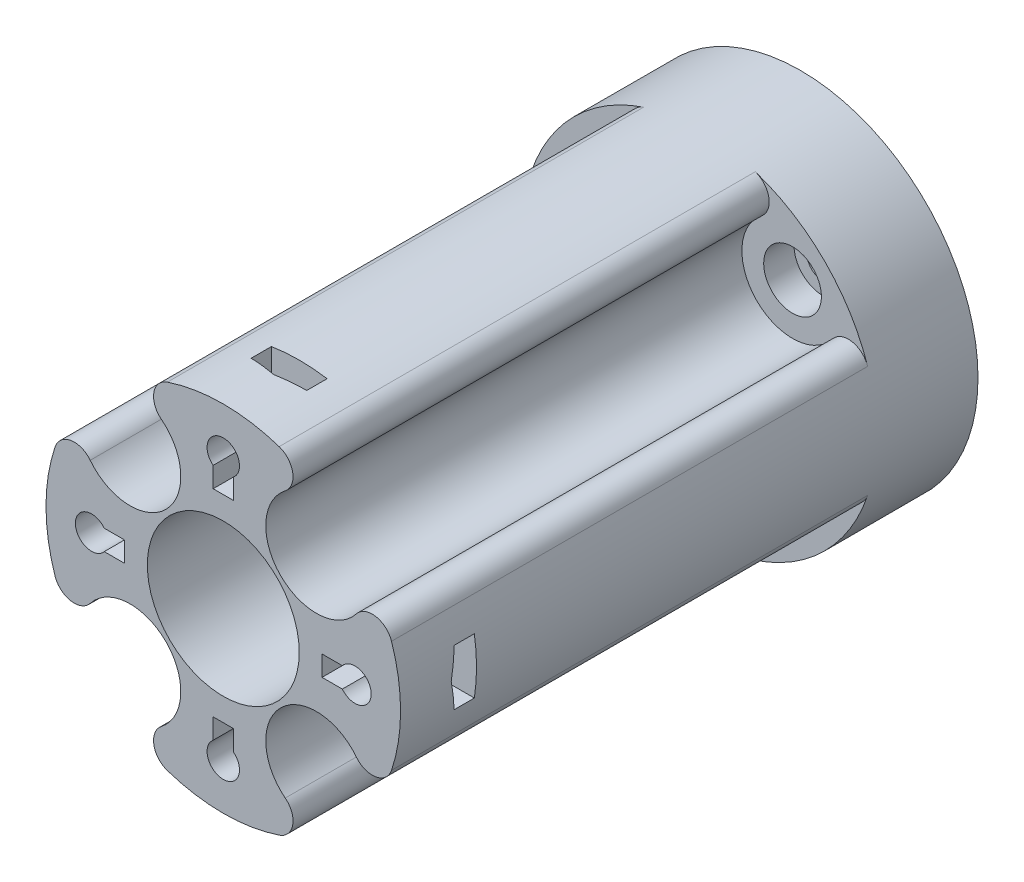
SolidWorks part; units mm, degrees
ref_plane "Front Plane" through (0, 0, 0) normal (1, 0, 0) x (0, 1, 0)
ref_plane "Top Plane" through (0, 0, 0) normal (0, 0, 1) x (0, 1, 0)
ref_plane "Right Plane" through (0, 0, 0) normal (0, 1, 0) x (-1, 0, 0)
sketch "Sketch1" plane through (0, 0, 0) normal (0, 0, 1) x (0, 1, 0)
  line L0 (0, 0) -> (9.1924, 9.1924) construction
  circle A0 centre (0, 0) radius 17.5
  circle A1 centre (0, 0) radius 13 construction
  circle A2 centre (9.1924, 9.1924) radius 1.6
  circle A3 centre (9.1924, 9.1924) radius 2.85
  circle A4 centre (9.1924, -9.1924) radius 2.85
  circle A5 centre (9.1924, -9.1924) radius 1.6
  circle A6 centre (-9.1924, -9.1924) radius 2.85
  circle A7 centre (-9.1924, -9.1924) radius 1.6
  circle A8 centre (-9.1924, 9.1924) radius 2.85
  circle A9 centre (-9.1924, 9.1924) radius 1.6
  circle A10 centre (0, 13) radius 1.65
  circle A11 centre (13, 0) radius 1.65
  circle A12 centre (0, -13) radius 1.65
  circle A13 centre (-13, 0) radius 1.65
  point P19 (0, 0)
  dimension "D1" = 35
  dimension "D2" = 26
  dimension "D3" = 3.2
  dimension "D4" = 5.7
  dimension "D6" = 3.3
  dimension "D5" = 4
  dimension "D7" = 4
extrude "Boss-Extrude1" add sketch "Sketch1" along normal blind 57 contours A0 A8 A6 A4 A3 | A10 | A13 | A12 | A11 region at (0, 0, 0) region at (-13, 0, 0) region at (0, 13, 0) region at (13, 0, 0) region at (0, -13, 0)
extrude "Boss-Extrude2" add sketch "Sketch1<3>" along normal blind 7 contours A6 A7 | A8 A9 | A4 A5 | A3 A2 region at (-9.1924, 6.423, 0) region at (9.1924, 6.423, 0) region at (9.1924, -11.9618, 0) region at (-9.1924, -11.9618, 0)
sketch "Sketch1<3>" plane through (0, 0, 0) normal (0, 0, 1) x (0, 1, 0) same geometry as "Sketch1"
sketch "Sketch2" plane through (0, 0, 57) normal (0, 0, 1) x (1, 0, 0)
  circle A0 centre (-9.1924, 9.1924) radius 5
  circle A1 centre (9.1924, 9.1924) radius 5
  circle A2 centre (9.1924, -9.1924) radius 5
  circle A3 centre (-9.1924, -9.1924) radius 5
  dimension "D1" = 10
  dimension "D2" = 2
  dimension "D3" = 2
extrude "Cut-Extrude1" cut sketch "Sketch2" against normal offset from surface (47 mm away) 3 up to face at (-7.5924, -9.1924, 7)
fillet "Fillet1" radius 2 8 edges at (14.0286, 10.4618, 33.5) (-14.0286, 10.4618, 33.5) (-10.4618, 14.0286, 33.5) (10.4618, 14.0286, 33.5) (14.0286, -10.4618, 33.5) (10.4618, -14.0286, 33.5) (-10.4618, -14.0286, 33.5) (-14.0286, -10.4618, 33.5)
sketch "Sketch3" plane through (0, 0, 57) normal (0, 0, 1) x (1, 0, 0)
  line L0 (-2.75, 15.75) -> (-2.75, 17.2826)
  line L2 (-2.75, 15.75) -> (-2.75, 10.25)
  line L3 (-2.75, 10.25) -> (2.75, 10.25)
  line L4 (2.75, 15.75) -> (2.75, 10.25)
  line L5 (-2.75, 15.75) -> (2.75, 10.25) construction
  line L6 (-2.75, 10.25) -> (2.75, 15.75) construction
  line L7 (2.75, 15.75) -> (2.75, 17.2826)
  line L8 (15.75, -2.75) -> (10.25, -2.75)
  line L9 (10.25, 2.75) -> (10.25, -2.75)
  line L10 (15.75, 2.75) -> (10.25, 2.75)
  line L11 (15.75, 2.75) -> (17.2826, 2.75)
  line L12 (15.75, -2.75) -> (17.2826, -2.75)
  line L13 (-2.75, -15.75) -> (-2.75, -10.25)
  line L14 (2.75, -10.25) -> (-2.75, -10.25)
  line L15 (2.75, -15.75) -> (2.75, -10.25)
  line L16 (2.75, -15.75) -> (2.75, -17.2826)
  line L17 (-2.75, -15.75) -> (-2.75, -17.2826)
  line L18 (-15.75, 2.75) -> (-10.25, 2.75)
  line L19 (-10.25, -2.75) -> (-10.25, 2.75)
  line L20 (-15.75, -2.75) -> (-10.25, -2.75)
  line L21 (-15.75, -2.75) -> (-17.2826, -2.75)
  line L22 (-15.75, 2.75) -> (-17.2826, 2.75)
  circle A0 centre (0, 0) radius 13 construction
  circle A2 centre (0, 13) radius 1.6
  arc A3 (5.5152, 16.6082) -> (-5.5152, 16.6082) centre (0, 0) ccw construction
  arc A4 (-2.75, 17.2826) -> (2.75, 17.2826) centre (0, 0) cw
  arc A5 (17.2826, 2.75) -> (17.2826, -2.75) centre (0, 0) cw
  circle A6 centre (13, 0) radius 1.6
  arc A7 (2.75, -17.2826) -> (-2.75, -17.2826) centre (0, 0) cw
  circle A8 centre (0, -13) radius 1.6
  arc A9 (-17.2826, -2.75) -> (-17.2826, 2.75) centre (0, 0) cw
  circle A10 centre (-13, 0) radius 1.6
  point P41 (0, 0)
  dimension "D1" = 26
  dimension "D2" = 3.2
  dimension "D3" = 5.5
  dimension "D4" = 5.5
  dimension "D5" = 4
extrude "Cut-Extrude2" cut sketch "Sketch3" against normal blind 2.5 from offset 5 offset against normal yes
extrude "Cut-Extrude3" cut sketch "Sketch3<2>" against normal blind 10 contours A10 | A2 | A6 | A8 region at (0, 13, 57) region at (13, 0, 57) region at (0, -13, 57) region at (-13, 0, 57)
sketch "Sketch3<2>" plane through (0, 0, 57) normal (0, 0, 1) x (1, 0, 0) same geometry as "Sketch3"
chamfer "Chamfer1" distance 2.75 distance2 0.5 8 edges at (-13.7663, -2.75, 52) (-2.75, 13.7663, 52) (2.75, 13.7663, 52) (13.7663, 2.75, 52) (13.7663, -2.75, 52) (2.75, -13.7663, 52) (-2.75, -13.7663, 52) (-13.7663, 2.75, 52) first distance on face at (-14.6, 0, 52) first distance on face at (-1.6, 13, 52) first distance on face at (11.4, 0, 52) first distance on face at (-1.6, -13, 52)
sketch "Sketch4" plane through (0, 0, 57) normal (0, 0, 1) x (1, 0, 0)
  circle A0 centre (0, 0) radius 7.5
  dimension "D1" = 15
extrude "Cut-Extrude4" cut sketch "Sketch4" against normal through all contours A0
extrude "Cut-Extrude5" cut sketch "Sketch1<4>" along normal blind 3 contours A13 | A12 | A11 | A10 region at (-13, 0, 0) region at (0, 13, 0) region at (13, 0, 0) region at (0, -13, 0)
sketch "Sketch1<4>" plane through (0, 0, 0) normal (0, 0, 1) x (0, 1, 0) same geometry as "Sketch1"
sketch "Sketch5" plane through (0, 0, 57) normal (0, 0, 1) x (1, 0, 0)
  line L0 (-10.25, -2.75) -> (-10.25, 2.75) construction
  line L1 (-2.75, 10.25) -> (2.75, 10.25) construction
  line L2 (10.25, 2.75) -> (10.25, -2.75) construction
  line L3 (2.75, -10.25) -> (-2.75, -10.25) construction
  line L4 (-10.25, -2.75) -> (-10.25, 2.75)
  line L5 (-2.75, 10.25) -> (2.75, 10.25)
  line L6 (10.25, 2.75) -> (10.25, -2.75)
  line L7 (2.75, -10.25) -> (-2.75, -10.25)
  line L8 (0, 10.25) -> (0, 9.75) construction
  line L13 (10.25, 0) -> (9.75, 0) construction
  line L14 (-1, 9.75) -> (1, 9.75)
  line L15 (-1, 9.75) -> (-1, 13)
  line L16 (-1, 13) -> (1, 13)
  line L17 (1, 9.75) -> (1, 13)
  line L18 (9.75, -1) -> (13, -1)
  line L19 (13, 1) -> (13, -1)
  line L20 (9.75, 1) -> (13, 1)
  line L21 (9.75, 1) -> (9.75, -1)
  line L22 (0, -10.25) -> (0, -9.75) construction
  line L23 (-1, -9.75) -> (-1, -13)
  line L24 (1, -13) -> (-1, -13)
  line L25 (1, -9.75) -> (1, -13)
  line L26 (1, -9.75) -> (-1, -9.75)
  line L27 (-10.25, 0) -> (-9.75, 0) construction
  line L28 (-9.75, 1) -> (-13, 1)
  line L29 (-13, -1) -> (-13, 1)
  line L30 (-9.75, -1) -> (-13, -1)
  line L31 (-9.75, -1) -> (-9.75, 1)
  point P14 (0, 9.75)
  point P15 (0, 13)
  point P16 (0, 13)
  dimension "D1" = 0.5
  dimension "D2" = 2
  dimension "D3" = 4
extrude "Cut-Extrude6" cut sketch "Sketch5" against normal up to surface (7.5 mm away) contours L30 L29 L28 L31 | L14 L17 L16 L15 | L18 L19 L20 L21 | L24 L23 L26 L25 up to face at (-1.6, -13, 49.5)
